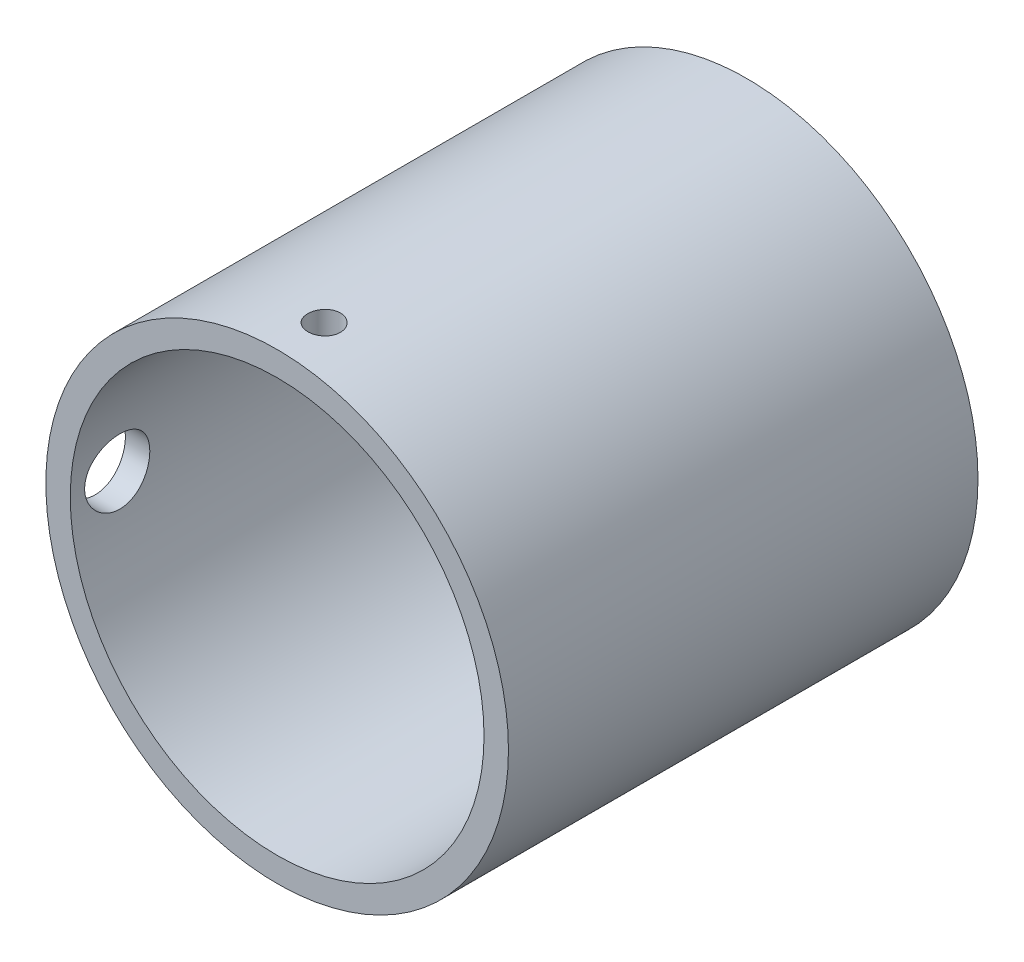
SolidWorks part; units mm, degrees
ref_plane "Front Plane" through (0, 0, 0) normal (0, 0, 1) x (1, 0, 0)
ref_plane "Top Plane" through (0, 0, 0) normal (0, 1, 0) x (1, 0, 0)
ref_plane "Right Plane" through (0, 0, 0) normal (1, 0, 0) x (0, 0, -1)
sketch "Sketch1" plane through (0, 0, 0) normal (0, 0, 1) x (1, 0, 0)
  circle A0 centre (0, 0) radius 6.35
  circle A1 centre (0, 0) radius 7.1
  dimension "D1" = 12.7
  dimension "D2" = 14.2
extrude "Boss-Extrude1" add sketch "Sketch1" against normal up to surface (14.4125 mm away)
sketch "Sketch3" plane through (0, 0, 0) normal (1, 0, 0) x (0, 0, -1)
  circle A0 centre (1.4407, 0) radius 1
  dimension "D1" = 2
sketch "Sketch4" plane through (0, 0, 0) normal (0, 1, 0) x (1, 0, 0)
  line L0 (0, 0.4407) -> (0, 2.4407) construction
  circle A0 centre (0, 1.4407) radius 0.5
  dimension "D1" = 1
extrude "Cut-Extrude1" cut sketch "Sketch3" against normal through all
extrude "Cut-Extrude2" cut sketch "Sketch4" along normal through all
